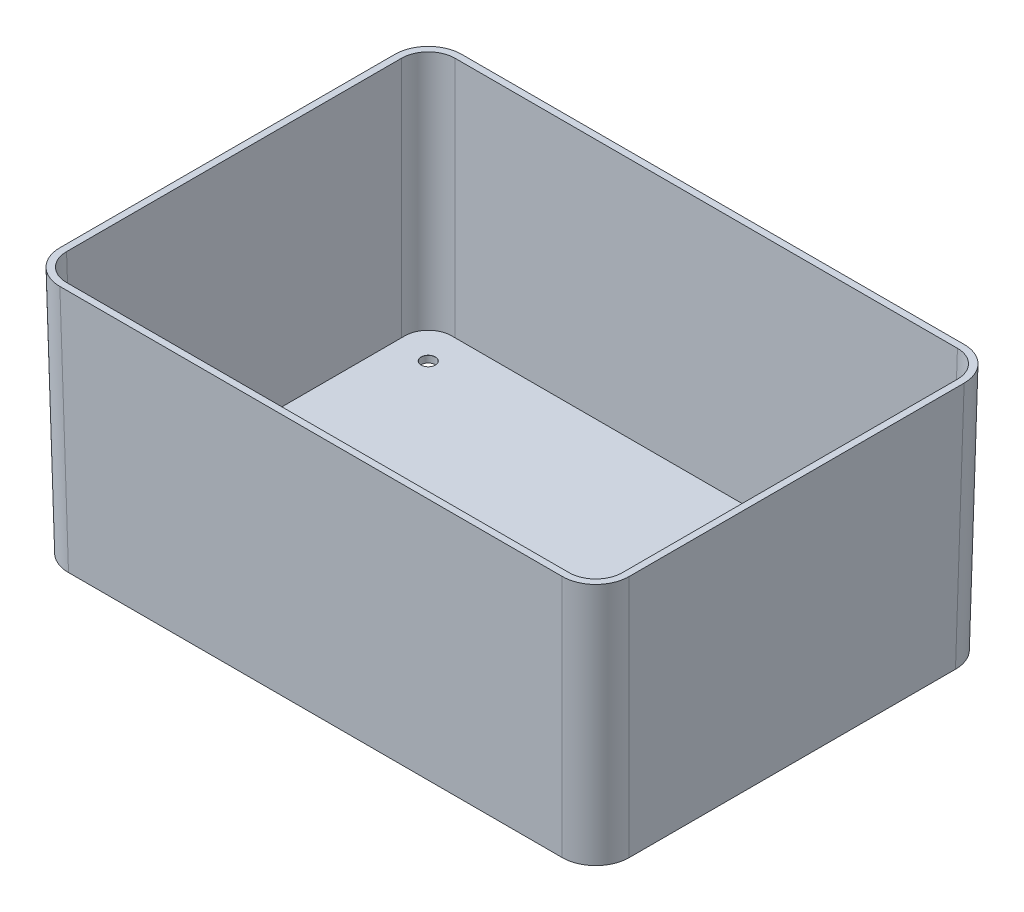
SolidWorks part; units mm, degrees
material "ABS PC"
ref_plane "Front Plane" through (0, 0, 0) normal (0, 0, 1) x (1, 0, 0)
ref_plane "Top Plane" through (0, 0, 0) normal (0, 1, 0) x (1, 0, 0)
ref_plane "Right Plane" through (0, 0, 0) normal (1, 0, 0) x (0, 0, -1)
sketch "Sketch1" plane through (0, 0, 0) normal (0, 1, 0) x (1, 0, 0)
  line L1 (-85, 60) -> (85, 60)
  line L2 (-85, 60) -> (-85, -60)
  line L3 (-85, -60) -> (85, -60)
  line L4 (85, 60) -> (85, -60)
  line L5 (-85, 60) -> (85, -60) construction
  line L6 (-85, -60) -> (85, 60) construction
  point P0 (0, 0)
  dimension "D1" = 120
  dimension "D2" = 170
extrude "Boss-Extrude1" add sketch "Sketch1" along normal blind 74
draft "Draft1" type of draft neutral plane draft angle 1 faces to draft 4 face at (-85, 37, 0) face at (0, 37, -60) face at (85, 37, 0) face at (0, 37, 60) neutral plane through (0, 74, 0) neutral plane normal (0, 1, 0) reverse direction yes parameters "D1"=1
fillet "Fillet1" radius 10 4 edges at (-84.3542, 37, 59.3542) (-84.3542, 37, -59.3542) (84.3542, 37, -59.3542) (84.3542, 37, 59.3542)
sketch "Sketch2" plane through (0, 0, 0) normal (0, -1, 0) x (1, 0, 0)
  line L8 (73.7098, 53.7083) -> (-73.7098, 53.7083)
  line L9 (-78.7083, 48.7098) -> (-78.7083, -48.7098)
  line L10 (-73.7098, -53.7083) -> (73.7098, -53.7083)
  line L11 (78.7083, -48.7098) -> (78.7083, 48.7098)
  line L12 (73.7098, 53.7083) -> (-73.7098, 53.7083)
  line L13 (-78.7083, 48.7098) -> (-78.7083, -48.7098)
  line L14 (-73.7098, -53.7083) -> (73.7098, -53.7083)
  line L15 (78.7083, -48.7098) -> (78.7083, 48.7098)
  spline S0 degree 3 poles (352.0874, -1899.784) (33.8628, -215.1427) (-44.3164, 59.6418) (-74.8433, 53.5809) (-75.0016, 53.5414) (-75.3155, 53.4464) (-75.4715, 53.3906) (-75.9253, 53.2027) (-76.2123, 53.0493) (-76.7555, 52.687) (-77.0127, 52.4761) (-77.4738, 52.0154) (-77.6807, 51.764) (-78.0461, 51.2181) (-78.2015, 50.9274) (-78.451, 50.3264) (-78.547, 50.0121) (-86.7808, 8.7849) (420.7544, -89.4109) (1890.7834, -294.5338) knots -11.765063 -11.765063 -11.765063 -11.765063 0.125 0.125 0.1875 0.1875 0.25 0.25 0.375 0.375 0.5 0.5 0.625 0.625 0.75 0.75 0.875 0.875 16.710768 16.710768 16.710768 16.710768 only from (-73.7098, 53.7083) to (-78.7083, 48.7098)
  spline S1 degree 3 poles (1874.784, 377.0874) (190.1427, 58.8628) (-84.6418, -19.3164) (-78.5809, -49.8433) (-78.5414, -50.0016) (-78.4464, -50.3155) (-78.3906, -50.4715) (-78.2027, -50.9253) (-78.0493, -51.2123) (-77.687, -51.7555) (-77.4761, -52.0127) (-77.0154, -52.4738) (-76.764, -52.6807) (-76.2181, -53.0461) (-75.9274, -53.2015) (-75.3264, -53.451) (-75.0121, -53.547) (-33.7849, -61.7808) (64.4109, 445.7544) (269.5338, 1915.7834) knots -11.765063 -11.765063 -11.765063 -11.765063 0.125 0.125 0.1875 0.1875 0.25 0.25 0.375 0.375 0.5 0.5 0.625 0.625 0.75 0.75 0.875 0.875 16.710768 16.710768 16.710768 16.710768 only from (-78.7083, -48.7098) to (-73.7098, -53.7083)
  spline S2 degree 3 poles (-352.0874, 1899.784) (-33.8628, 215.1427) (44.3164, -59.6418) (74.8433, -53.5809) (75.0016, -53.5414) (75.3155, -53.4464) (75.4715, -53.3906) (75.9253, -53.2027) (76.2123, -53.0493) (76.7555, -52.687) (77.0127, -52.4761) (77.4738, -52.0154) (77.6807, -51.764) (78.0461, -51.2181) (78.2015, -50.9274) (78.451, -50.3264) (78.547, -50.0121) (86.7808, -8.7849) (-420.7544, 89.4109) (-1890.7834, 294.5338) knots -11.765063 -11.765063 -11.765063 -11.765063 0.125 0.125 0.1875 0.1875 0.25 0.25 0.375 0.375 0.5 0.5 0.625 0.625 0.75 0.75 0.875 0.875 16.710768 16.710768 16.710768 16.710768 only from (73.7098, -53.7083) to (78.7083, -48.7098)
  spline S3 degree 3 poles (-1874.784, -377.0874) (-190.1427, -58.8628) (84.6418, 19.3164) (78.5809, 49.8433) (78.5414, 50.0016) (78.4464, 50.3155) (78.3906, 50.4715) (78.2027, 50.9253) (78.0493, 51.2123) (77.687, 51.7555) (77.4761, 52.0127) (77.0154, 52.4738) (76.764, 52.6807) (76.2181, 53.0461) (75.9274, 53.2015) (75.3264, 53.451) (75.0121, 53.547) (33.7849, 61.7808) (-64.4109, -445.7544) (-269.5338, -1915.7834) knots -11.765063 -11.765063 -11.765063 -11.765063 0.125 0.125 0.1875 0.1875 0.25 0.25 0.375 0.375 0.5 0.5 0.625 0.625 0.75 0.75 0.875 0.875 16.710768 16.710768 16.710768 16.710768 only from (78.7083, 48.7098) to (73.7098, 53.7083)
  spline S4 degree 3 poles (-73.7098, 53.7083) (-74.0399, 53.7083) (-74.3644, 53.676) (-74.8433, 53.5809) (-75.0016, 53.5414) (-75.3155, 53.4464) (-75.4715, 53.3906) (-75.9253, 53.2027) (-76.2123, 53.0493) (-76.7555, 52.687) (-77.0127, 52.4761) (-77.4738, 52.0154) (-77.6807, 51.764) (-78.0461, 51.2181) (-78.2015, 50.9274) (-78.451, 50.3264) (-78.547, 50.0121) (-78.676, 49.3663) (-78.7083, 49.0399) (-78.7083, 48.7098) knots 0 0 0 0 0.125 0.125 0.1875 0.1875 0.25 0.25 0.375 0.375 0.5 0.5 0.625 0.625 0.75 0.75 0.875 0.875 1 1 1 1
  spline S5 degree 3 poles (-78.7083, -48.7098) (-78.7083, -49.0399) (-78.676, -49.3644) (-78.5809, -49.8433) (-78.5414, -50.0016) (-78.4464, -50.3155) (-78.3906, -50.4715) (-78.2027, -50.9253) (-78.0493, -51.2123) (-77.687, -51.7555) (-77.4761, -52.0127) (-77.0154, -52.4738) (-76.764, -52.6807) (-76.2181, -53.0461) (-75.9274, -53.2015) (-75.3264, -53.451) (-75.0121, -53.547) (-74.3663, -53.676) (-74.0399, -53.7083) (-73.7098, -53.7083) knots 0 0 0 0 0.125 0.125 0.1875 0.1875 0.25 0.25 0.375 0.375 0.5 0.5 0.625 0.625 0.75 0.75 0.875 0.875 1 1 1 1
  spline S6 degree 3 poles (73.7098, -53.7083) (74.0399, -53.7083) (74.3644, -53.676) (74.8433, -53.5809) (75.0016, -53.5414) (75.3155, -53.4464) (75.4715, -53.3906) (75.9253, -53.2027) (76.2123, -53.0493) (76.7555, -52.687) (77.0127, -52.4761) (77.4738, -52.0154) (77.6807, -51.764) (78.0461, -51.2181) (78.2015, -50.9274) (78.451, -50.3264) (78.547, -50.0121) (78.676, -49.3663) (78.7083, -49.0399) (78.7083, -48.7098) knots 0 0 0 0 0.125 0.125 0.1875 0.1875 0.25 0.25 0.375 0.375 0.5 0.5 0.625 0.625 0.75 0.75 0.875 0.875 1 1 1 1
  spline S7 degree 3 poles (78.7083, 48.7098) (78.7083, 49.0399) (78.676, 49.3644) (78.5809, 49.8433) (78.5414, 50.0016) (78.4464, 50.3155) (78.3906, 50.4715) (78.2027, 50.9253) (78.0493, 51.2123) (77.687, 51.7555) (77.4761, 52.0127) (77.0154, 52.4738) (76.764, 52.6807) (76.2181, 53.0461) (75.9274, 53.2015) (75.3264, 53.451) (75.0121, 53.547) (74.3663, 53.676) (74.0399, 53.7083) (73.7098, 53.7083) knots 0 0 0 0 0.125 0.125 0.1875 0.1875 0.25 0.25 0.375 0.375 0.5 0.5 0.625 0.625 0.75 0.75 0.875 0.875 1 1 1 1
  dimension "D1" = 5
extrude "Cut-Extrude1" cut sketch "Sketch2" against normal blind 2
shell "Shell1" thickness 2 removed face at (0, 74, 0)
hole_wizard "Ø4.2 (4.2) Diameter Hole1" positions "Sketch3" profile "Sketch4" hole size "Ø4.2" standard "ISO" end condition through all
sketch "Sketch3" plane through (0, 4, 0) normal (0, 1, 0) x (1, 0, 0)
  line L12 (70.7083, -45.7083) -> (70.7083, 45.7083)
  line L13 (70.7083, 45.7083) -> (-70.7083, 45.7083)
  line L14 (-70.7083, 45.7083) -> (-70.7083, -45.7083)
  line L15 (-70.7083, -45.7083) -> (70.7083, -45.7083)
  line L16 (70.7083, -45.7083) -> (70.7083, 45.7083)
  line L17 (70.7083, 45.7083) -> (-70.7083, 45.7083)
  line L18 (-70.7083, 45.7083) -> (-70.7083, -45.7083)
  line L19 (-70.7083, -45.7083) -> (70.7083, -45.7083)
  point P49 (70.7083, -45.7083)
  point P50 (70.7083, 45.7083)
  point P51 (-70.7083, 45.7083)
  point P52 (-70.7083, -45.7083)
  dimension "D1" = 10
sketch "Sketch4" plane through (70.7083, 4, 45.7083) normal (1, 0, 0) x (0, 0, 1)
  line L0 (0, 0) -> (0, 4.01)
  line L1 (0, 4.01) -> (2.1, 4.01)
  line L2 (2.1, 4.01) -> (2.1, 0.025)
  line L3 (2.1, 0.025) -> (2.125, 0)
  line L5 (2.125, 0) -> (0, 0)
  line L6 (-2.1, 0.025) -> (-2.125, 0) construction
  line L11 (0, -6.35) -> (0, 107.95) construction
  dimension "Thru Hole Dia." = 4.2
  dimension "Thru Hole Depth" = 4.01
  dimension "Near C'Sink Dia." = 4.25
  dimension "Near C'Sink Angle" = 90
